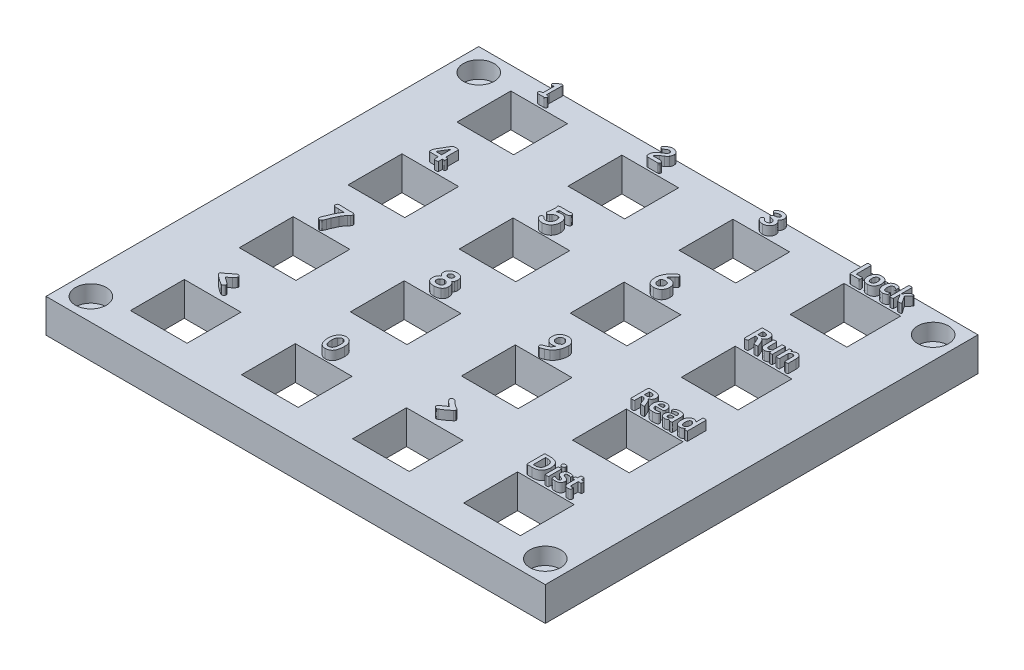
SolidWorks part; units mm, degrees
ref_plane "Front Plane" through (0, 0, 0) normal (0, 0, 1) x (1, 0, 0)
ref_plane "Top Plane" through (0, 0, 0) normal (0, 1, 0) x (1, 0, 0)
ref_plane "Right Plane" through (0, 0, 0) normal (1, 0, 0) x (0, 0, -1)
sketch "Sketch1" plane through (0, 0, 0) normal (0, 1, 0) x (1, 0, 0)
  line L1 (-56.515, 48.9797) -> (56.515, 48.9797)
  line L2 (-56.515, 48.9797) -> (-56.515, -48.9797)
  line L3 (-56.515, -48.9797) -> (56.515, -48.9797)
  line L4 (56.515, 48.9797) -> (56.515, -48.9797)
  line L5 (-56.515, 48.9797) -> (56.515, -48.9797) construction
  line L6 (-56.515, -48.9797) -> (56.515, 48.9797) construction
  point P0 (0, 0)
  dimension "D1" = 113.03
  dimension "D2" = 97.9594
extrude "Boss-Extrude1" add sketch "Sketch1" along normal blind 7.62
sketch "Sketch2" plane through (0, 7.62, 0) normal (0, 1, 0) x (1, 0, 0)
  line L0 (-56.515, 48.9797) -> (-44.1706, 48.9797) construction
  line L1 (56.515, 48.9797) -> (-56.515, 48.9797) construction
  line L2 (-44.1706, 48.9797) -> (-44.1706, 43.8997) construction
  line L3 (-44.1706, 43.8997) -> (-56.515, 43.8997) construction
  line L4 (-56.515, 48.9797) -> (-56.515, -48.9797) construction
  line L5 (-44.1706, 19.2617) -> (-31.3436, 19.2617)
  line L6 (-44.1706, 43.8997) -> (-31.3436, 43.8997)
  line L7 (-44.1706, 43.8997) -> (-44.1706, 31.7077)
  line L8 (-44.1706, 31.7077) -> (-31.3436, 31.7077)
  line L9 (-31.3436, 43.8997) -> (-31.3436, 31.7077)
  line L10 (-44.1706, 19.2617) -> (-44.1706, 7.0697)
  line L11 (-44.1706, 7.0697) -> (-31.3436, 7.0697)
  line L46 (-31.3436, 19.2617) -> (-31.3436, 7.0697)
  line L59 (-44.1706, -5.3763) -> (-31.3436, -5.3763)
  line L60 (-44.1706, -5.3763) -> (-44.1706, -17.5683)
  line L61 (-44.1706, -17.5683) -> (-31.3436, -17.5683)
  line L62 (-31.3436, -5.3763) -> (-31.3436, -17.5683)
  line L75 (-44.1706, -30.0143) -> (-31.3436, -30.0143)
  line L76 (-44.1706, -30.0143) -> (-44.1706, -42.2063)
  line L77 (-44.1706, -42.2063) -> (-31.3436, -42.2063)
  line L78 (-31.3436, -30.0143) -> (-31.3436, -42.2063)
  line L91 (-19.0246, 19.2617) -> (-6.1976, 19.2617)
  line L92 (-19.0246, 43.8997) -> (-6.1976, 43.8997)
  line L93 (-19.0246, 43.8997) -> (-19.0246, 31.7077)
  line L94 (-19.0246, 31.7077) -> (-6.1976, 31.7077)
  line L95 (-6.1976, 43.8997) -> (-6.1976, 31.7077)
  line L96 (-19.0246, 19.2617) -> (-19.0246, 7.0697)
  line L97 (-19.0246, 7.0697) -> (-6.1976, 7.0697)
  line L98 (-6.1976, 19.2617) -> (-6.1976, 7.0697)
  line L99 (-19.0246, -5.3763) -> (-6.1976, -5.3763)
  line L100 (-19.0246, -5.3763) -> (-19.0246, -17.5683)
  line L101 (-19.0246, -17.5683) -> (-6.1976, -17.5683)
  line L102 (-6.1976, -5.3763) -> (-6.1976, -17.5683)
  line L103 (-19.0246, -30.0143) -> (-6.1976, -30.0143)
  line L104 (-19.0246, -30.0143) -> (-19.0246, -42.2063)
  line L105 (-19.0246, -42.2063) -> (-6.1976, -42.2063)
  line L106 (-6.1976, -30.0143) -> (-6.1976, -42.2063)
  line L107 (-19.0246, 48.9797) -> (-19.0246, 43.8997) construction
  line L108 (-19.0246, 43.8997) -> (-31.369, 43.8997) construction
  line L109 (6.1214, 19.2617) -> (18.9484, 19.2617)
  line L110 (6.1214, 43.8997) -> (18.9484, 43.8997)
  line L111 (6.1214, 43.8997) -> (6.1214, 31.7077)
  line L112 (6.1214, 31.7077) -> (18.9484, 31.7077)
  line L113 (18.9484, 43.8997) -> (18.9484, 31.7077)
  line L114 (6.1214, 19.2617) -> (6.1214, 7.0697)
  line L115 (6.1214, 7.0697) -> (18.9484, 7.0697)
  line L116 (18.9484, 19.2617) -> (18.9484, 7.0697)
  line L117 (6.1214, -5.3763) -> (18.9484, -5.3763)
  line L118 (6.1214, -5.3763) -> (6.1214, -17.5683)
  line L119 (6.1214, -17.5683) -> (18.9484, -17.5683)
  line L120 (18.9484, -5.3763) -> (18.9484, -17.5683)
  line L121 (6.1214, -30.0143) -> (18.9484, -30.0143)
  line L122 (6.1214, -30.0143) -> (6.1214, -42.2063)
  line L123 (6.1214, -42.2063) -> (18.9484, -42.2063)
  line L124 (18.9484, -30.0143) -> (18.9484, -42.2063)
  line L125 (6.1214, 48.9797) -> (6.1214, 43.8997) construction
  line L126 (6.1214, 43.8997) -> (-6.223, 43.8997) construction
  line L127 (31.2674, 19.2617) -> (44.0944, 19.2617)
  line L128 (31.2674, 43.8997) -> (44.0944, 43.8997)
  line L129 (31.2674, 43.8997) -> (31.2674, 31.7077)
  line L130 (31.2674, 31.7077) -> (44.0944, 31.7077)
  line L131 (44.0944, 43.8997) -> (44.0944, 31.7077)
  line L132 (31.2674, 19.2617) -> (31.2674, 7.0697)
  line L133 (31.2674, 7.0697) -> (44.0944, 7.0697)
  line L134 (44.0944, 19.2617) -> (44.0944, 7.0697)
  line L135 (31.2674, -5.3763) -> (44.0944, -5.3763)
  line L136 (31.2674, -5.3763) -> (31.2674, -17.5683)
  line L137 (31.2674, -17.5683) -> (44.0944, -17.5683)
  line L138 (44.0944, -5.3763) -> (44.0944, -17.5683)
  line L139 (31.2674, -30.0143) -> (44.0944, -30.0143)
  line L140 (31.2674, -30.0143) -> (31.2674, -42.2063)
  line L141 (31.2674, -42.2063) -> (44.0944, -42.2063)
  line L142 (44.0944, -30.0143) -> (44.0944, -42.2063)
  line L143 (31.2674, 48.9797) -> (31.2674, 43.8997) construction
  line L144 (31.2674, 43.8997) -> (18.923, 43.8997) construction
  dimension "D1" = 12.3444
  dimension "D2" = 5.08
  dimension "D3" = 12.827
  dimension "D4" = 12.192
  dimension "D5" = 4
  dimension "D6" = 12.827
  dimension "D7" = 4
extrude "Cut-Extrude1" cut sketch "Sketch2" against normal blind 7.62
sketch "Sketch8" plane through (0, 7.62, 0) normal (0, 1, 0) x (1, 0, 0)
  line L0 (-46.355, 48.9797) -> (-56.515, 38.8197) construction
  line L1 (-56.515, 48.9797) -> (-46.355, 48.9797)
  line L2 (-56.515, 48.9797) -> (-56.515, 38.8197)
  line L3 (-56.515, 38.8197) -> (-46.355, 38.8197)
  line L4 (-46.355, 48.9797) -> (-46.355, 38.8197)
  line L5 (56.515, 48.9797) -> (46.355, 48.9797)
  line L6 (56.515, 48.9797) -> (56.515, 38.8197)
  line L7 (56.515, 38.8197) -> (46.355, 38.8197)
  line L8 (46.355, 48.9797) -> (46.355, 38.8197)
  line L9 (56.515, -48.9797) -> (46.355, -48.9797)
  line L10 (56.515, -48.9797) -> (56.515, -38.8197)
  line L11 (56.515, -38.8197) -> (46.355, -38.8197)
  line L12 (46.355, -48.9797) -> (46.355, -38.8197)
  line L13 (-56.515, -48.9797) -> (-46.355, -48.9797)
  line L14 (-56.515, -48.9797) -> (-56.515, -38.8197)
  line L15 (-56.515, -38.8197) -> (-46.355, -38.8197)
  line L16 (-46.355, -48.9797) -> (-46.355, -38.8197)
  line L17 (-46.355, -38.8197) -> (-56.515, -48.9797) construction
  line L18 (56.515, -38.8197) -> (46.355, -48.9797) construction
  line L19 (56.515, 48.9797) -> (46.355, 38.8197) construction
  circle A0 centre (-51.435, 43.8997) radius 3.4925
  circle A1 centre (51.435, 43.8997) radius 3.4925
  circle A2 centre (51.435, -43.8997) radius 3.4925
  circle A3 centre (-51.435, -43.8997) radius 3.4925
  circle A4 centre (-51.435, 43.8997) radius 1.7018
  circle A5 centre (51.435, 43.8997) radius 1.7018
  circle A6 centre (-51.435, -43.8997) radius 1.7018
  circle A7 centre (51.435, -43.8997) radius 1.7018
  dimension "D1" = 10.16
  dimension "D2" = 10.16
  dimension "D3" = 10.16
  dimension "D4" = 10.16
  dimension "D5" = 10.16
  dimension "D6" = 10.16
  dimension "D7" = 10.16
  dimension "D8" = 10.16
sketch "Sketch9" plane through (0, 7.62, 0) normal (0, 1, 0) x (1, 0, 0)
  line L0 (-37.7571, 43.8997) -> (-37.7571, 44.4077) construction
  line L1 (-31.3436, 43.8997) -> (-44.1706, 43.8997) construction
  line L2 (-31.3436, 43.8997) -> (-31.3436, 48.9797) construction
  line L3 (56.515, 48.9797) -> (-56.515, 48.9797) construction
  line L4 (-6.1976, 43.8997) -> (-6.1976, 48.9797) construction
  line L5 (18.9484, 43.8997) -> (18.9484, 48.9797) construction
  line L6 (44.0944, 43.8997) -> (44.0944, 48.9797) construction
  line L7 (-44.1706, 43.8997) -> (-44.1706, 48.9797) construction
  line L8 (-19.0246, 43.8997) -> (-19.0246, 48.9797) construction
  line L9 (6.1214, 43.8997) -> (6.1214, 48.9797) construction
  line L10 (31.2674, 43.8997) -> (31.2674, 48.9797) construction
  line L11 (-44.1706, 44.4077) -> (-31.3436, 44.4077) construction
  line L12 (-31.3436, 44.4077) -> (-19.0246, 44.4077) construction
  line L13 (-19.0246, 44.4077) -> (-6.1976, 44.4077) construction
  line L14 (-6.1976, 44.4077) -> (6.1214, 44.4077) construction
  line L15 (6.1214, 44.4077) -> (18.9484, 44.4077) construction
  line L16 (18.9484, 44.4077) -> (31.2674, 44.4077) construction
  line L17 (31.2674, 44.4077) -> (44.0944, 44.4077) construction
  line L18 (37.6809, 31.7077) -> (37.6809, 31.1997) construction
  line L19 (31.2674, 31.7077) -> (44.0944, 31.7077) construction
  line L20 (-37.7571, 19.2617) -> (-37.7571, 19.7697) construction
  line L21 (-31.3436, 19.2617) -> (-44.1706, 19.2617) construction
  line L22 (37.6809, 7.0697) -> (37.6809, 6.5617) construction
  line L23 (31.2674, 7.0697) -> (44.0944, 7.0697) construction
  line L24 (-37.7571, -5.3763) -> (-37.7571, -4.8683) construction
  line L25 (-31.3436, -5.3763) -> (-44.1706, -5.3763) construction
  line L26 (37.6809, -30.0143) -> (37.6809, -29.5063) construction
  line L27 (44.0944, -30.0143) -> (31.2674, -30.0143) construction
  line L28 (-44.1706, 19.7697) -> (-31.3436, 19.7697) construction
  line L29 (-31.3436, 19.7697) -> (-19.0246, 19.7697) construction
  line L30 (-19.0246, 19.7697) -> (-6.1976, 19.7697) construction
  line L31 (-6.1976, 19.7697) -> (6.1214, 19.7697) construction
  line L32 (6.1214, 19.7697) -> (18.9484, 19.7697) construction
  line L33 (18.9484, 19.7697) -> (31.2674, 19.7697) construction
  line L34 (31.2674, 19.7697) -> (44.0944, 19.7697) construction
  line L35 (44.0944, 19.7697) -> (44.0944, -4.8683) construction
  line L36 (31.2674, -4.8683) -> (56.515, -4.8683) construction
  line L37 (31.2674, -4.8683) -> (18.9484, -4.8683) construction
  line L38 (18.9484, -4.8683) -> (6.1214, -4.8683) construction
  line L39 (6.1214, -4.8683) -> (-6.1976, -4.8683) construction
  line L40 (-6.1976, -4.8683) -> (-19.0246, -4.8683) construction
  line L41 (-19.0246, -4.8683) -> (-31.3436, -4.8683) construction
  line L42 (-31.3436, -4.8683) -> (-44.1706, -4.8683) construction
  line L43 (-44.1706, -4.8683) -> (-44.1706, -29.5063) construction
  line L44 (-44.1706, -29.5063) -> (-31.3436, -29.5063) construction
  line L45 (-31.3436, -29.5063) -> (-19.0246, -29.5063) construction
  line L46 (-19.0246, -29.5063) -> (-6.1976, -29.5063) construction
  line L47 (-6.1976, -29.5063) -> (6.1214, -29.5063) construction
  line L48 (6.1214, -29.5063) -> (18.9484, -29.5063) construction
  line L49 (18.9484, -29.5063) -> (31.2674, -29.5063) construction
  line L50 (31.2674, -29.5063) -> (44.0944, -29.5063) construction
  line L51 (56.515, -48.9797) -> (56.515, 48.9797) construction
  dimension "D1" = 0.508
  dimension "D2" = 0.508
  dimension "D3" = 0.508
  dimension "D4" = 0.508
  dimension "D5" = 0.508
  dimension "D6" = 0.508
extrude "Cut-Extrude2" cut sketch "Sketch8" against normal through all contours A4 | A5 | A7 | A6 region at (-51.435, 7.62, -43.8997) region at (51.435, 7.62, -43.8997) region at (-51.435, 7.62, 43.8997) region at (51.435, 7.62, 43.8997)
extrude "Cut-Extrude3" cut sketch "Sketch8<4>" against normal blind 3.81 contours A0 A4 | A1 A5 | A2 A7 | A3 A6 region at (-54.8287, 7.62, -43.8997) region at (48.0413, 7.62, -43.8997) region at (48.0413, 7.62, 43.8997) region at (-54.8287, 7.62, 43.8997)
sketch "Sketch8<4>" plane through (0, 7.62, 0) normal (0, 1, 0) x (1, 0, 0) same geometry as "Sketch8"
sketch "Sketch10" plane through (0, 7.62, 0) normal (0, 1, 0) x (1, 0, 0)
  text T0 "1" font "Comic Sans MS" height in points 16
  text T1 "2" font "Comic Sans MS" height 4.572
  text T2 "3" font "Comic Sans MS" height 4.572
  text T3 "Lock" font "Calibri" height 4.1148
  text T4 "Run" font "Calibri" height 4.1148
  text T5 "6" font "Comic Sans MS" height in points 18
  text T6 "5" font "Comic Sans MS" height in points 18
  text T7 "4" font "Calibri" height in points 18
  text T8 "7" font "Comic Sans MS" height in points 18
  text T9 "8" font "Comic Sans MS" height in points 18
  text T10 "9" font "Comic Sans MS" height in points 18
  text T11 "Read" font "Calibri" height 4.1148
  text T12 "Dist" font "Calibri" height 4.1148
  text T13 ">" font "Comic Sans MS" height in points 22
  text T14 "0" font "Comic Sans MS" height in points 16
  text T15 ">" font "Comic Sans MS" height in points 22
extrude "Boss-Extrude2" add sketch "Sketch10" along normal blind 2.032
